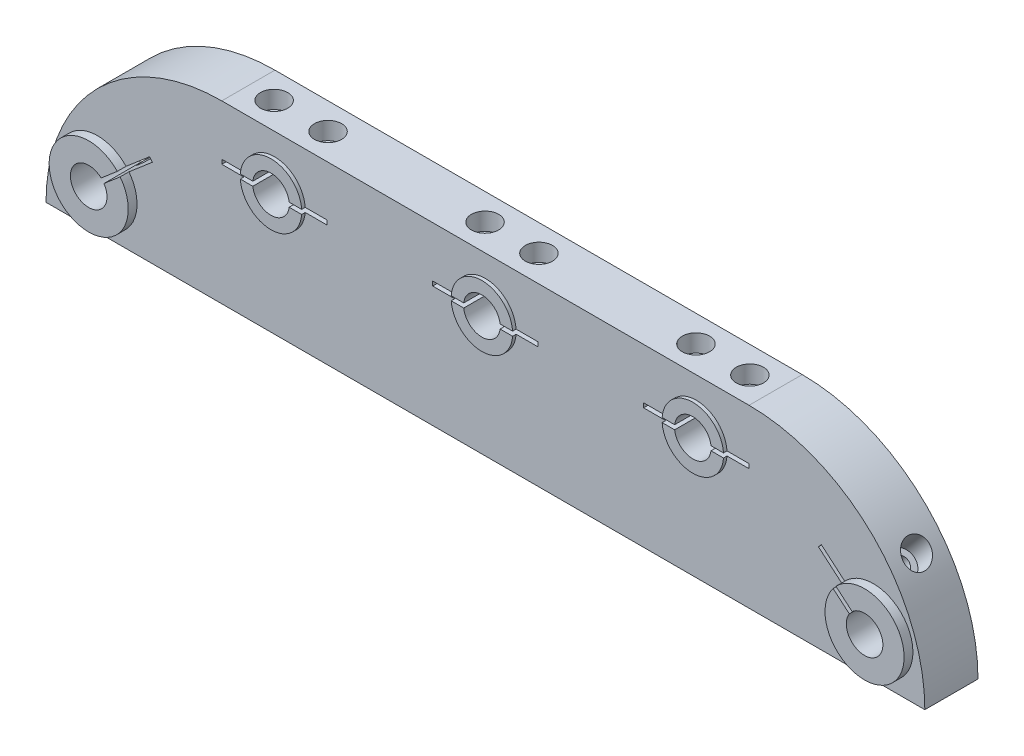
SolidWorks part; units mm, degrees
ref_plane "Front Plane" through (0, 0, 0) normal (0, 0, 1) x (1, 0, 0)
ref_plane "Top Plane" through (0, 0, 0) normal (0, 1, 0) x (1, 0, 0)
ref_plane "Right Plane" through (0, 0, 0) normal (1, 0, 0) x (0, 0, -1)
sketch "Sketch1" plane through (0, 0, 0) normal (0, 0, 1) x (1, 0, 0)
  line L0 (-48, 8) -> (0, 8) construction
  line L1 (-60, 20) -> (60, 20)
  line L3 (-100, -20) -> (100, -20)
  line L5 (-100, 20) -> (100, -20) construction
  line L6 (-100, -20) -> (100, 20) construction
  line L7 (0, 8) -> (48, 8) construction
  line L8 (0, 37.7846) -> (0, -45.3301) construction
  line L9 (-110.8398, 0) -> (122.7505, 0) construction
  circle A0 centre (0, 8) radius 4.165
  circle A1 centre (48, 8) radius 4.165
  circle A2 centre (-48, 8) radius 4.165
  circle A3 centre (-88.2843, -10) radius 4.165
  circle A4 centre (88.2843, -10) radius 4.165
  circle A5 centre (-48, 8) radius 19 construction
  arc A7 (-60, 20) -> (-100, -20) centre (-60, -20) ccw
  arc A8 (60, 20) -> (100, -20) centre (60, -20) cw
  circle A9 centre (-88.2843, -10) radius 10 construction
  circle A10 centre (88.2843, -10) radius 10 construction
  point P0 (0, 0)
  point P25 (0, 20)
  point P26 (0, -20)
  dimension "D4" = 8.33
  dimension "D6" = 38
  dimension "D1" = 40
  dimension "D2" = 200
  dimension "D3" = 12
  dimension "D5" = 48
  dimension "D7" = 40
  dimension "D8" = 200
extrude "Boss-Extrude1" add sketch "Sketch1" along normal blind 12.1
sketch "Sketch2" plane through (0, 0, 12.1) normal (0, 0, 1) x (1, 0, 0)
  circle A1 centre (48, 8) radius 4.165 construction
  circle A2 centre (0, 8) radius 4.165 construction
  circle A3 centre (-48, 8) radius 4.165 construction
  circle A6 centre (48, 8) radius 4.165
  circle A7 centre (0, 8) radius 4.165
  circle A8 centre (-48, 8) radius 4.165
  circle A11 centre (-48, 8) radius 7
  circle A12 centre (0, 8) radius 7
  circle A13 centre (48, 8) radius 7
  dimension "D1" = 14
extrude "Boss-Extrude3" add sketch "Sketch2" along normal blind 0.8
sketch "Sketch4" plane through (0, 0, 12.1) normal (0, 0, 1) x (1, 0, 0)
  circle A0 centre (88.2843, -10) radius 4.165 construction
  circle A1 centre (-88.2843, -10) radius 4.165 construction
  circle A2 centre (88.2843, -10) radius 4.165
  circle A3 centre (-88.2843, -10) radius 4.165
  circle A4 centre (-88.2843, -10) radius 9
  circle A5 centre (88.2843, -10) radius 9
  dimension "D1" = 18
extrude "Boss-Extrude4" add sketch "Sketch4" along normal blind 2
sketch "Sketch6" plane through (0, 0, 0) normal (0, 0, -1) x (-1, 0, 0)
  line L0 (-48, 8) -> (48, 8) construction
  line L1 (-100, -20) -> (-67.196, 8) construction
  line L2 (100, -20) -> (67.196, 8) construction
  line L3 (0, 24.4792) -> (0, -10) construction
  line L11 (20, 8.3) -> (20, 7.7)
  line L16 (88.6089, -9.6197) -> (76.4392, 0.7678)
  line L17 (88.6089, -9.6197) -> (87.9597, -10.3803)
  line L18 (87.9597, -10.3803) -> (75.79, 0.0072)
  line L19 (76.4392, 0.7678) -> (75.79, 0.0072)
  line L20 (-87.9597, -10.3803) -> (-75.79, 0.0072)
  line L21 (-76.4392, 0.7678) -> (-75.79, 0.0072)
  line L22 (-88.6089, -9.6197) -> (-76.4392, 0.7678)
  line L23 (-88.6089, -9.6197) -> (-87.9597, -10.3803)
  line L37 (-60, 8.5) -> (-36, 8.5)
  line L38 (-60, 8.5) -> (-60, 7.5)
  line L39 (-60, 7.5) -> (-36, 7.5)
  line L40 (-36, 8.5) -> (-36, 7.5)
  line L41 (-60, 8.5) -> (-36, 7.5) construction
  line L42 (-60, 7.5) -> (-36, 8.5) construction
  line L43 (-12, 8.5) -> (12, 8.5)
  line L44 (-12, 8.5) -> (-12, 7.5)
  line L45 (-12, 7.5) -> (12, 7.5)
  line L46 (12, 8.5) -> (12, 7.5)
  line L47 (-12, 8.5) -> (12, 7.5) construction
  line L48 (-12, 7.5) -> (12, 8.5) construction
  line L49 (36, 8.5) -> (60, 8.5)
  line L50 (36, 8.5) -> (36, 7.5)
  line L51 (36, 7.5) -> (60, 7.5)
  line L52 (60, 8.5) -> (60, 7.5)
  line L53 (36, 8.5) -> (60, 7.5) construction
  line L54 (36, 7.5) -> (60, 8.5) construction
  circle A1 centre (-88.2843, -10) radius 4.165 construction
  circle A2 centre (-88.2843, -10) radius 4.165 construction
  circle A3 centre (88.2843, -10) radius 4.165 construction
  circle A4 centre (88.2843, -10) radius 4.165 construction
  point P6 (-48, 8)
  point P7 (0, 0)
  point P24 (0, 8)
  point P29 (48, 8)
  point P32 (88.2843, -10)
  point P46 (0, 0)
  point P47 (0, 0)
  point P48 (0, 8)
  circle M18 centre (-48, 8) radius 4.165
  dimension "D1" = 24
  dimension "D2" = 1
  dimension "D3" = 1
  dimension "D4" = 16
extrude "Cut-Extrude2" cut sketch "Sketch6" against normal through all both and the other way through all contours L38 L39 L37 M18 | L37 L40 L39 L38 | L43 L46 L45 L44 | L49 L52 L51 L50 | L20 L21 L22 L23 | L16 L19 L18 L17 region at (56.0775, 8, 0)
sketch "Sketch8" plane through (0, 7.5, 0) normal (0, 1, 0) x (1, 0, 0)
  line L0 (52.1349, 0) -> (52.1349, -12.9) construction
  line L1 (60, -12.1) -> (60, 0) construction
  line L2 (60, -12.1) -> (60, 0) construction
  line L3 (62.9889, -6.05) -> (-85.4727, -6.05) construction
  line L4 (43.8651, -12.9) -> (43.8651, 0) construction
  line L6 (4.1349, 0) -> (4.1349, -12.9) construction
  line L7 (0, -7.755) -> (0, 7.755) construction
  circle A0 centre (54.1349, -6.05) radius 1.6
  circle A1 centre (41.8651, -6.05) radius 1.6
  circle A2 centre (6.1349, -6.05) radius 1.6
  circle A3 centre (-41.8651, -6.05) radius 1.6
  circle A4 centre (-6.1349, -6.05) radius 1.6
  circle A5 centre (-54.1349, -6.05) radius 1.6
  point P12 (0, 0)
  point P13 (60, -6.05)
  point P14 (0, 0)
  point P15 (0, 0)
  point P16 (0, 0)
  dimension "D1" = 3.2
  dimension "D2" = 2
  dimension "D4" = 2
  dimension "D3" = 2
extrude "Cut-Extrude3" cut sketch "Sketch8" against normal through all both and the other way through all
sketch "Sketch9" plane through (31.9476, 37.429, 0) normal (0.6492, 0.7606, 0) x (0.7606, -0.6492, 0)
  line L0 (69.5067, -14.1) -> (69.5067, 0) construction
  line L1 (57.6415, -12.1) -> (57.6415, 0) construction
  line L2 (57.6415, -12.1) -> (57.6415, 0) construction
  circle A0 centre (67.5067, -6.05) radius 1.75
  point P6 (57.6415, -6.05)
  dimension "D1" = 3.5
  dimension "D2" = 2
extrude "Cut-Extrude4" cut sketch "Sketch9" against normal up to next and the other way up to next
sketch "Sketch10" plane through (-31.9476, 37.429, 0) normal (-0.6492, 0.7606, 0) x (0.7606, 0.6492, 0)
  line L0 (-57.6415, -12.1) -> (-57.6415, 0) construction
  line L1 (-57.6415, -12.1) -> (-57.6415, 0) construction
  line L2 (-69.5067, -14.1) -> (-69.5067, 0) construction
  circle A0 centre (-67.5067, -6.05) radius 1.75
  point P6 (-57.6415, -6.05)
  dimension "D1" = 3.5
  dimension "D2" = 2
extrude "Cut-Extrude5" cut sketch "Sketch10" against normal up to next and the other way up to next
sketch "Sketch11" plane through (0, 20, 0) normal (0, 1, 0) x (1, 0, 0)
  circle A0 centre (-54.1349, -6.05) radius 3.1
  circle A1 centre (-41.8651, -6.05) radius 3.1
  circle A2 centre (-6.1349, -6.05) radius 3.1
  circle A3 centre (6.1349, -6.05) radius 3.1
  circle A4 centre (41.8651, -6.05) radius 3.1
  circle A5 centre (54.1349, -6.05) radius 3.1
  dimension "D1" = 6.2
extrude "Cut-Extrude6" cut sketch "Sketch11" against normal blind 4
sketch "Sketch12" plane through (0, -20, 0) normal (0, -1, 0) x (1, 0, 0)
  circle A0 centre (-54.1349, 6.05) radius 3.7
  circle A1 centre (-41.8651, 6.05) radius 3.7
  circle A2 centre (-6.1349, 6.05) radius 3.7
  circle A3 centre (6.1349, 6.05) radius 3.7
  circle A4 centre (41.8651, 6.05) radius 3.7
  circle A5 centre (54.1349, 6.05) radius 3.7
  dimension "D1" = 7.4
extrude "Cut-Extrude7" cut sketch "Sketch12" against normal blind 20
ref_plane "Plane1" through (-37.1414, 43.5138, 0) normal (0.6492, -0.7606, 0) x (-0.7606, -0.6492, 0)
sketch "Sketch13" plane through (-37.1414, 43.5138, 0) normal (0.6492, -0.7606, 0) x (-0.7606, -0.6492, 0)
  circle A0 centre (67.5067, -6.05) radius 3.1
  dimension "D1" = 6.2
extrude "Cut-Extrude8" cut sketch "Sketch13" against normal up to next
ref_plane "Plane2" through (-27.4031, 32.1047, 0) normal (-0.6492, 0.7606, 0) x (0.7606, 0.6492, 0)
sketch "Sketch14" plane through (-27.4031, 32.1047, 0) normal (-0.6492, 0.7606, 0) x (0.7606, 0.6492, 0)
  circle A0 centre (-67.5067, -6.05) radius 3.6
  dimension "D1" = 7.2
extrude "Cut-Extrude9" cut sketch "Sketch14" against normal up to next
ref_plane "Plane3" through (27.4031, 32.1047, 0) normal (0.6492, 0.7606, 0) x (0.7606, -0.6492, 0)
sketch "Sketch15" plane through (27.4031, 32.1047, 0) normal (0.6492, 0.7606, 0) x (0.7606, -0.6492, 0)
  circle A0 centre (67.5067, -6.05) radius 3.6
  dimension "D1" = 7.2
extrude "Cut-Extrude10" cut sketch "Sketch15" against normal up to next
ref_plane "Plane4" through (37.1414, 43.5138, 0) normal (-0.6492, -0.7606, 0) x (-0.7606, 0.6492, 0)
sketch "Sketch16" plane through (37.1414, 43.5138, 0) normal (-0.6492, -0.7606, 0) x (-0.7606, 0.6492, 0)
  circle A0 centre (-67.5067, -6.05) radius 3.1
  dimension "D1" = 6.2
extrude "Cut-Extrude11" cut sketch "Sketch16" against normal up to next
